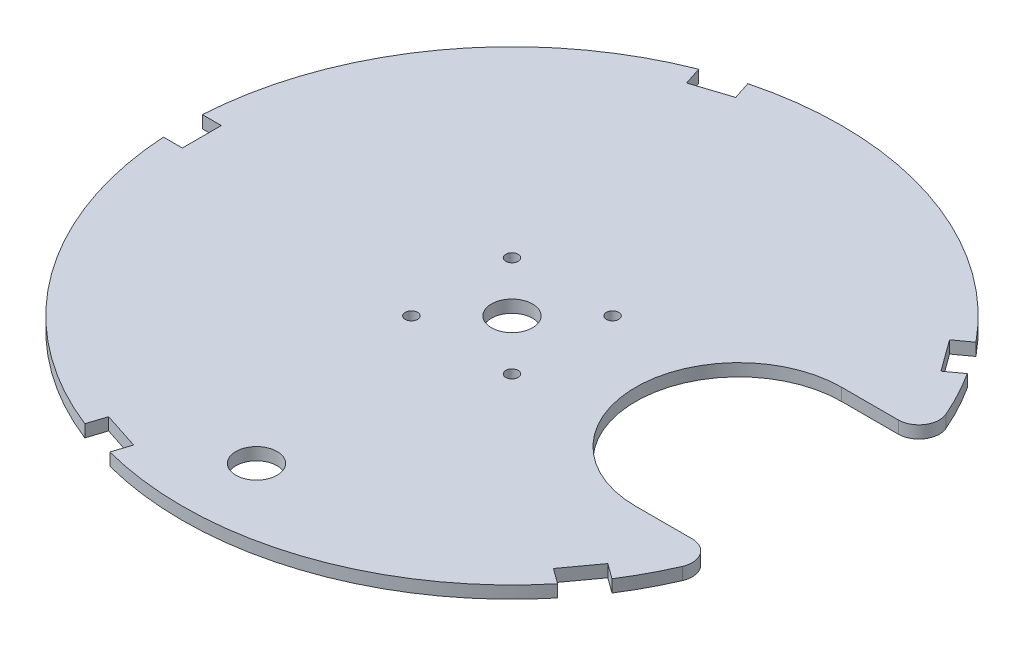
SolidWorks part; units mm, degrees
ref_plane "Front Plane" through (0, 0, 0) normal (0, 0, 1) x (1, 0, 0)
ref_plane "Top Plane" through (0, 0, 0) normal (0, 1, 0) x (1, 0, 0)
ref_plane "Right Plane" through (0, 0, 0) normal (1, 0, 0) x (0, 0, -1)
sketch "Sketch1" plane through (0, 0, 0) normal (0, 1, 0) x (1, 0, 0)
  line L0 (69.85, -31.75) -> (96.5116, -31.75)
  line L1 (-15.5, -15.5) -> (15.5, -15.5) construction
  line L2 (-15.5, -15.5) -> (-15.5, 15.5) construction
  line L3 (-15.5, 15.5) -> (15.5, 15.5) construction
  line L4 (15.5, -15.5) -> (15.5, 15.5) construction
  line L5 (-15.5, -15.5) -> (15.5, 15.5) construction
  line L6 (-15.5, 15.5) -> (15.5, -15.5) construction
  line L7 (69.85, 31.75) -> (96.5116, 31.75)
  line L8 (0, -69.85) -> (0, -78.74)
  line L9 (-95.6, 0) -> (-95.6, 6)
  line L10 (-95.6, 0) -> (-95.6, -6)
  line L11 (-95.6, 6) -> (-101.4227, 6)
  line L12 (-95.6, -6) -> (-101.4227, -6)
  line L13 (-35.2484, 89.0669) -> (-37.0477, 94.6046)
  line L14 (-29.542, 90.921) -> (-23.8357, 92.7751)
  line L15 (-29.542, 90.921) -> (-35.2484, 89.0669)
  line L16 (-23.8357, 92.7751) -> (-25.635, 98.3128)
  line L17 (73.8153, 61.0464) -> (78.526, 64.4689)
  line L18 (77.342, 56.1923) -> (80.8687, 51.3382)
  line L19 (77.342, 56.1923) -> (73.8153, 61.0464)
  line L20 (80.8687, 51.3382) -> (85.5794, 54.7607)
  line L21 (80.8687, -51.3382) -> (85.5794, -54.7607)
  line L22 (77.342, -56.1923) -> (73.8153, -61.0464)
  line L23 (77.342, -56.1923) -> (80.8687, -51.3382)
  line L24 (73.8153, -61.0464) -> (78.526, -64.4689)
  line L25 (-23.8357, -92.7751) -> (-25.635, -98.3128)
  line L26 (-29.542, -90.921) -> (-35.2484, -89.0669)
  line L27 (-29.542, -90.921) -> (-23.8357, -92.7751)
  line L28 (-35.2484, -89.0669) -> (-37.0477, -94.6046)
  circle A0 centre (0, 0) radius 101.6
  circle A1 centre (0, 0) radius 69.85 construction
  circle A2 centre (69.85, 0) radius 31.75
  circle A3 centre (0, -69.85) radius 19.05 construction
  circle A4 centre (0, -78.74) radius 6.35
  circle A7 centre (-15.5, 15.5) radius 1.905
  circle A8 centre (15.5, 15.5) radius 1.905
  circle A9 centre (15.5, -15.5) radius 1.905
  circle A10 centre (-15.5, -15.5) radius 1.905
  circle A11 centre (0, 0) radius 95.6 construction
  circle A12 centre (0, 0) radius 6.35
  circle A13 centre (0, 0) radius 88.9
  point P28 (0, 0)
  point P56 (0, 0)
  point P60 (0, 0)
  dimension "D1" = 203.2
  dimension "D2" = 31.75
  dimension "D3" = 63.5
  dimension "D6" = 38.1
  dimension "D7" = 8.89
  dimension "D8" = 12.7
  dimension "D9" = 3.81
  dimension "D11" = 6
  dimension "D15" = 12.7
  dimension "D16" = 12.7
  dimension "D4" = 31
  dimension "D5" = 31
  dimension "D12" = 6
  dimension "D13" = 6
  dimension "D10" = 4
  dimension "D14" = 5
extrude "Boss-Extrude1" add sketch "Sketch1" along normal blind 3.81 contours A4 A13 L0 A2 L7 A12 A10 A9 A8 A7 | A13 A4 L7 A0 L20 L18 L19 L17 L16 L14 L15 L13 L11 L9 L10 L12 L28 L26 L27 L25 L24 L22 L23 L21 L0 region at (-7.9883, 0, -0.4563) region at (89.7743, 0, 34.5867)
fillet "Fillet1" radius 6.35 2 edges at (96.5116, 1.905, 31.75) (96.5116, 1.905, -31.75)
